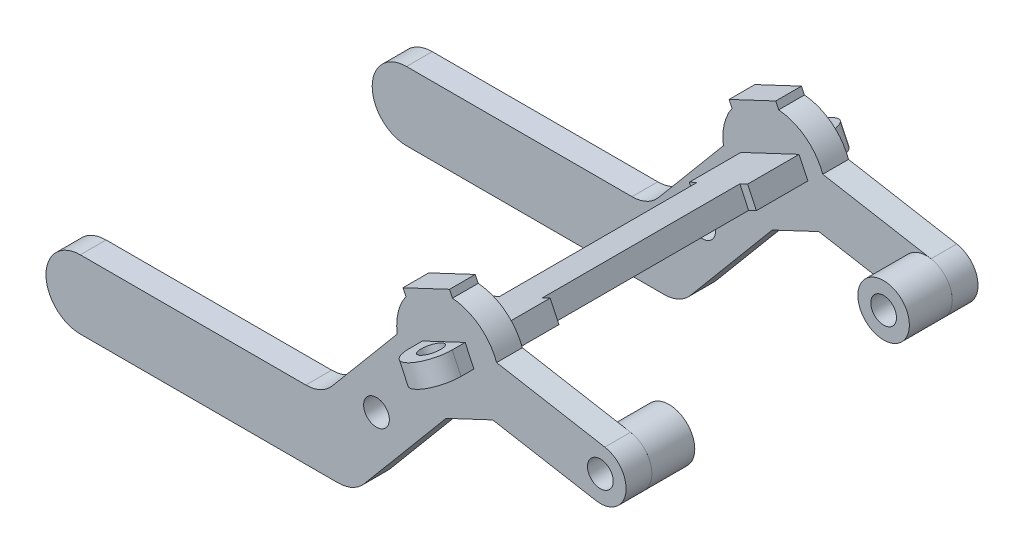
SolidWorks part; units mm, degrees
material "ﾎﾟﾘｵｷｼﾒﾁﾚﾝ(POM)ｱｾﾀｰﾙ共重合体"
ref_plane "正面" through (0, 0, 0) normal (0, 0, 1) x (1, 0, 0)
ref_plane "平面" through (0, 0, 0) normal (0, 1, 0) x (1, 0, 0)
ref_plane "右側面" through (0, 0, 0) normal (1, 0, 0) x (0, 0, -1)
sketch "ｽｹｯﾁ1" plane through (0, 0, 0) normal (0, 0, 1) x (1, 0, 0)
  line L0 (0, 0) -> (-12.8558, -15.3209) construction
  line L1 (-2.0411, -2.4325) -> (1.0861, -2.9839) construction
  line L2 (1.0861, -2.9839) -> (3.1272, -0.5514) construction
  line L3 (3.1272, -0.5514) -> (2.0411, 2.4325) construction
  line L4 (2.0411, 2.4325) -> (-1.0861, 2.9839) construction
  line L5 (-1.0861, 2.9839) -> (-3.1272, 0.5514) construction
  line L6 (-3.1272, 0.5514) -> (-2.0411, -2.4325) construction
  line L7 (-12.8558, -15.3209) -> (-42.8558, -15.3209) construction
  line L8 (-5.9388, -0.8547) -> (-13.522, -9.892)
  line L9 (-16.5862, -11.3209) -> (-42.8558, -11.3209)
  line L10 (-0.2465, -6.5167) -> (-9.7916, -17.892)
  line L11 (-12.8558, -19.3209) -> (-42.8558, -19.3209)
  line L12 (-3.0642, 2.5712) -> (-14.721, -11.3209) construction
  line L13 (-14.721, -11.3209) -> (-42.8558, -11.3209) construction
  line L14 (3.0642, -2.5712) -> (-10.9905, -19.3209) construction
  line L15 (-10.9905, -19.3209) -> (-42.8558, -19.3209) construction
  line L16 (5.6382, 2.0521) -> (18.2475, -0.1712)
  line L18 (17.2056, -6.0801) -> (5.1814, -3.9599)
  line L23 (17.7265, -3.1257) -> (0, 0) construction
  line L24 (0.1572, 6.7064) -> (0.4997, 5.9792)
  line L25 (-1.9769, -2.2565) -> (-2.9987, -0.0872)
  line L26 (-1.9769, -2.2565) -> (2.9987, 0.0872)
  line L27 (2.9987, 0.0872) -> (1.9769, 2.2565)
  line L28 (-2.9987, -0.0872) -> (1.9769, 2.2565)
  line L29 (-1.9769, -2.2565) -> (1.9769, 2.2565) construction
  line L30 (2.9987, 0.0872) -> (-2.9987, -0.0872) construction
  line L31 (0.1572, 6.7064) -> (-5.2708, 4.1496)
  line L32 (5.1814, -3.9599) -> (-0.2465, -6.5167)
  line L33 (-5.2708, 4.1496) -> (-4.9282, 3.4224)
  line L34 (0.1572, 6.7064) -> (-0.2465, -6.5167) construction
  line L35 (5.1814, -3.9599) -> (-5.2708, 4.1496) construction
  line L36 (2.4675, -5.2383) -> (-2.5568, 5.428) construction
  line L37 (5.1814, -3.9599) -> (4.5963, -3.8567) construction
  line L38 (0.1895, -5.997) -> (-0.2465, -6.5167) construction
  line L39 (-0.4997, -5.9792) -> (-0.2465, -6.5167) construction
  line L40 (-2.1239, -2.5311) -> (-0.4997, -5.9792) construction
  line L41 (-4.9282, 3.4224) -> (-2.1239, -2.5311) construction
  line L42 (4.9282, -3.4224) -> (5.1814, -3.9599) construction
  line L43 (3.6165, -0.6377) -> (4.9282, -3.4224) construction
  line L44 (0.4997, 5.9792) -> (3.6165, -0.6377) construction
  circle A0 centre (0, 0) radius 2.75 construction
  arc A2 (-42.8558, -11.3209) -> (-42.8558, -19.3209) centre (-42.8558, -15.3209) ccw
  arc A3 (-13.522, -9.892) -> (-16.5862, -11.3209) centre (-16.5862, -7.3209) cw
  arc A4 (-9.7916, -17.892) -> (-12.8558, -19.3209) centre (-12.8558, -15.3209) cw
  arc A5 (5.6382, 2.0521) -> (0.4997, 5.9792) centre (0, 0) ccw
  arc A6 (18.2475, -0.1712) -> (17.2056, -6.0801) centre (17.7265, -3.1257) cw
  arc A7 (4.5963, -3.8567) -> (5.6382, 2.0521) centre (0, 0) ccw construction
  arc A8 (0.1895, -5.997) -> (2.5568, -5.428) centre (0, 0) ccw construction
  arc A9 (-3.8567, -4.5963) -> (0.1895, -5.997) centre (0, 0) ccw construction
  arc A10 (-5.9388, -0.8547) -> (-3.8567, -4.5963) centre (0, 0) ccw construction
  circle A11 centre (17.7265, -3.1257) radius 1.5
  circle A12 centre (-8.3562, -9.9586) radius 1.5
  arc A13 (-4.9282, 3.4224) -> (-5.9388, -0.8547) centre (0, 0) ccw
  arc A14 (0.1356, 5.9985) -> (-2.5568, 5.428) centre (0, 0) ccw construction
  arc A15 (0.4997, 5.9792) -> (0.1356, 5.9985) centre (0, 0) ccw construction
  arc A16 (-2.5568, 5.428) -> (-4.7112, 3.7154) centre (0, 0) ccw construction
  arc A17 (-4.7112, 3.7154) -> (-4.9282, 3.4224) centre (0, 0) ccw construction
  arc A18 (2.5568, -5.428) -> (4.5963, -3.8567) centre (0, 0) ccw construction
  point P39 (-0.0447, 0.0948)
  dimension "D1" = 5.5
  dimension "D6" = 18
  dimension "D7" = 12
  dimension "D8" = 3
  dimension "D10" = 3
  dimension "D11" = 3
  dimension "D2" = 130
  dimension "D3" = 20
  dimension "D4" = 30
  dimension "D5" = 4
  dimension "D9" = 60
  dimension "D12" = 13
  dimension "D13" = 6
  dimension "D14" = 5.5
  dimension "D15" = 6
extrude "ﾎﾞｽ - 押し出し1" add sketch "ｽｹｯﾁ1" along normal mid plane 3
pattern_linear "直線ﾊﾟﾀｰﾝ1" count 2 spacing 38 along (0, 0, 1) of bodies 101
ref_plane "平面1" through (0, 0, 19) normal (0, 0, -1) x (-1, 0, 0)
sketch "ｽｹｯﾁ2" plane through (0, 0, 39.5) normal (0, 0, 1) x (1, 0, 0)
  line L5 (-2.9987, -0.0872) -> (-1.9769, -2.2565)
  line L6 (1.9769, 2.2565) -> (-2.9987, -0.0872)
  line L19 (2.9987, 0.0872) -> (1.9769, 2.2565)
  line L20 (-1.9769, -2.2565) -> (2.9987, 0.0872)
  line L21 (-2.9987, -0.0872) -> (-1.9769, -2.2565)
  line L22 (1.9769, 2.2565) -> (-2.9987, -0.0872)
  line L23 (2.9987, 0.0872) -> (1.9769, 2.2565)
  line L24 (-1.9769, -2.2565) -> (2.9987, 0.0872)
  circle A0 centre (0, 0) radius 1.6 construction
  dimension "D2" = 3.2
  dimension "D1" = 0
extrude "ﾎﾞｽ - 押し出し2" add sketch "ｽｹｯﾁ2" against normal up to surface (41 mm away) separate body up to face at (-6.8562, -9.9586, -1.5)
sketch "ｽｹｯﾁ4" plane through (0, 0, 1.5) normal (0, 0, 1) x (1, 0, 0)
  circle A0 centre (17.7265, -3.1257) radius 3
  circle A1 centre (17.7265, -3.1257) radius 1.5 construction
  circle A2 centre (17.7265, -3.1257) radius 1.5
  dimension "D1" = 6
extrude "ﾎﾞｽ - 押し出し3" add sketch "ｽｹｯﾁ4" along normal blind 5 separate body
mirror "ﾐﾗｰ1" about plane through (0, 0, 19) normal (0, 0, -1) of bodies 104
sketch "ｽｹｯﾁ5" plane through (-0.5109, 1.0847, 0) normal (-0.4261, 0.9047, 0) x (0, 0, 1)
  line L0 (0, 0) -> (4.5, 0) construction
  line L1 (1.5, 3.75) -> (7.5, 3.75)
  line L2 (1.5, 3.75) -> (1.5, -3.75)
  line L3 (1.5, -3.75) -> (7.5, -3.75)
  line L4 (7.5, 3.75) -> (7.5, -3.75)
  line L5 (1.5, 3.75) -> (7.5, -3.75) construction
  line L6 (1.5, -3.75) -> (7.5, 3.75) construction
  line L7 (-1.5, -2.75) -> (39.5, -2.75) construction
  line L8 (19, 14.2639) -> (19, -14.2639) construction
  line L9 (36.5, -3.75) -> (30.5, -3.75)
  line L10 (30.5, 3.75) -> (30.5, -3.75)
  line L11 (36.5, 3.75) -> (30.5, 3.75)
  line L12 (36.5, 3.75) -> (36.5, -3.75)
  line L13 (1.5, 2.75) -> (1.5, -2.75) construction
  line L14 (-1.5, 17.7046) -> (-1.5, 12.9743) construction
  line L15 (-3, -2.75) -> (-0.5, -2.75)
  line L16 (-3, -2.75) -> (-3, 2.75) construction
  line L17 (-3, 2.75) -> (-0.5, 2.75)
  line L18 (-0.5, -2.75) -> (-0.5, 2.75)
  line L19 (-3, -2.75) -> (-0.5, 2.75) construction
  line L20 (-3, 2.75) -> (-0.5, -2.75) construction
  line L21 (0, 0) -> (-1.75, 0) construction
  line L22 (41, -2.75) -> (38.5, -2.75)
  line L23 (38.5, -2.75) -> (38.5, 2.75)
  line L24 (41, 2.75) -> (38.5, 2.75)
  circle A0 centre (-3, 0) radius 1.5 construction
  arc A1 (-3, -2.75) -> (-3, 2.75) centre (-3, 0) cw
  arc A2 (41, -2.75) -> (41, 2.75) centre (41, 0) ccw
  circle A3 centre (41, 0) radius 1.5 construction
  circle A4 centre (-3, 0) radius 1.25
  circle A5 centre (41, 0) radius 1.25
  point P0 (4.5, 0)
  point P22 (-1.75, 0)
  dimension "D2" = 3
  dimension "D4" = 2.5
  dimension "D1" = 23
  dimension "D3" = 1
  dimension "D5" = 1
extrude "ﾎﾞｽ - 押し出し5" add sketch "ｽｹｯﾁ5" against normal up to surface (2.3979 mm away) up to face at (0.5109, -1.0847, 19)
